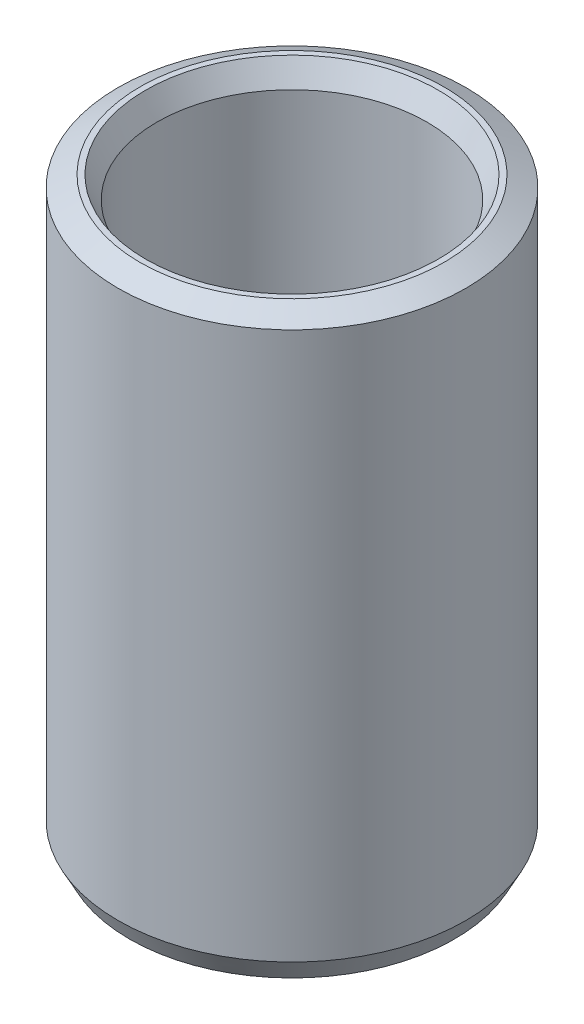
SolidWorks part; units mm, degrees
ref_plane "Front Plane" through (0, 0, 0) normal (0, 0, 1) x (1, 0, 0)
ref_plane "Top Plane" through (0, 0, 0) normal (0, 1, 0) x (1, 0, 0)
ref_plane "Right Plane" through (0, 0, 0) normal (1, 0, 0) x (0, 0, -1)
sketch "Sketch1" plane through (0, 0, 0) normal (0, 1, 0) x (1, 0, 0)
  circle A0 centre (0, 0) radius 12.5
  dimension "SLEEVE_OD" = 25
extrude "Boss-Extrude1" add sketch "Sketch1" along normal blind 41.7506
sketch "Sketch2" plane through (0, 0, 0) normal (0, 1, 0) x (1, 0, 0)
  circle A0 centre (0, 0) radius 9.698
  dimension "BORE_D" = 19.3959
extrude "Cut-Extrude1" cut sketch "Sketch2" along normal through all
chamfer "Chamfer1" distance 0.8244 angle 62.33 4 edges at (0, 41.7506, 9.698) (0, 0, 9.698) (0, 0, 12.5) (0, 41.7506, 12.5) first distance on face at (0, 41.7506, 9.698) first distance on face at (0, 0, 9.698) first distance on face at (0, 41.7506, 12.5)
